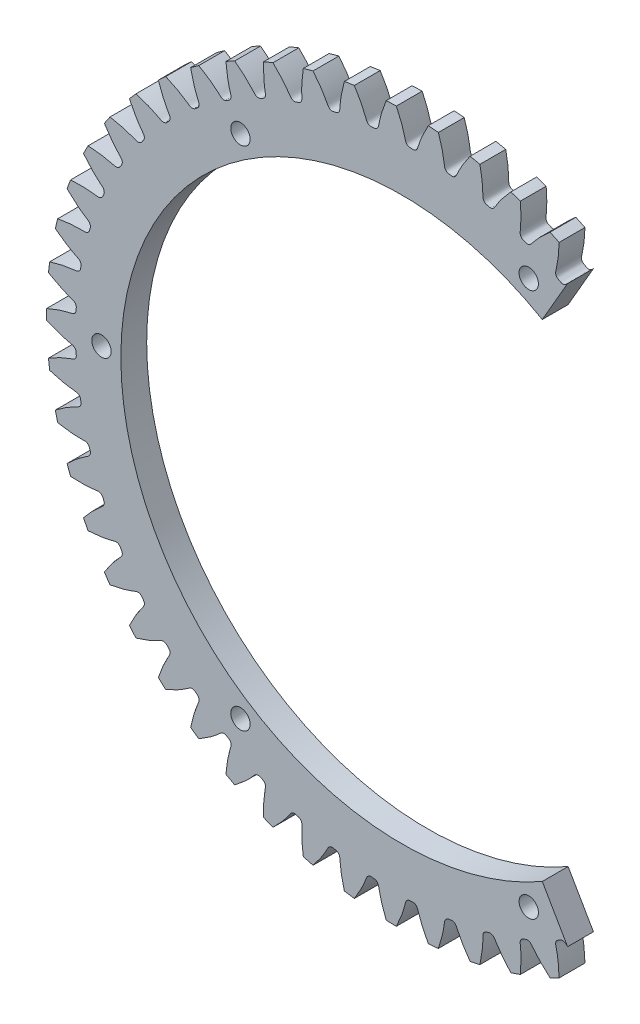
SolidWorks part; units mm, degrees
material "Thornel Mat VMA"
ref_plane "前视基准面" through (0, 0, 0) normal (0, 0, 1) x (1, 0, 0)
ref_plane "上视基准面" through (0, 0, 0) normal (0, 1, 0) x (1, 0, 0)
ref_plane "右视基准面" through (0, 0, 0) normal (1, 0, 0) x (0, 0, -1)
ref_axis "基准轴1" through (0, 0, 55) along (0, 0, -1)
sketch "旋转草图大直齿轮" plane through (0, 0, 0) normal (1, 0, 0) x (0, 0, -1)
  line L0 (0, 0) -> (1, 0) construction
  line L1 (-2, 0) -> (-2, 55)
  line L2 (-2, 55) -> (2, 55)
  line L3 (2, 55) -> (2, 0)
  line L4 (2, 0) -> (-2, 0)
revolve "大直齿轮" add sketch "旋转草图大直齿轮" angle 360 about L0
sketch "齿草图大直齿轮" plane through (0, 0, 0) normal (0, 0, 1) x (1, 0, 0)
  arc A0 (55.0418, 2.532) -> (55.0418, -2.532) centre (0, 0) cw
  spline S0 degree 3 poles (55.0418, -2.532) (54.9759, -2.4971) (54.8882, -2.451) (54.7785, -2.3944) (54.7135, -2.361) (54.6488, -2.3282) (54.5845, -2.2957) (54.5206, -2.2637) (54.457, -2.2321) (54.3937, -2.201) (54.3308, -2.1702) (54.2683, -2.1399) (54.2061, -2.1101) (54.1443, -2.0806) (54.0829, -2.0515) (54.0218, -2.0229) (53.9611, -1.9947) (53.9008, -1.9669) (53.8408, -1.9394) (53.7813, -1.9124) (53.7221, -1.8858) (53.6632, -1.8596) (53.6048, -1.8338) (53.5467, -1.8083) (53.4891, -1.7833) (53.4318, -1.7586) (53.3749, -1.7344) (53.3184, -1.7105) (53.2623, -1.6869) (53.2066, -1.6638) (53.1513, -1.641) (53.0964, -1.6186) (53.0418, -1.5966) (52.9877, -1.5749) (52.934, -1.5536) (52.8807, -1.5326) (52.8278, -1.512) (52.7753, -1.4918) (52.7232, -1.4719) (52.6716, -1.4523) (52.6203, -1.4331) (52.5695, -1.4143) (52.5191, -1.3957) (52.4691, -1.3776) (52.4195, -1.3597) (52.3703, -1.3422) (52.3216, -1.325) (52.2733, -1.3081) (52.2254, -1.2915) (52.178, -1.2753) (52.131, -1.2593) (52.0844, -1.2437) (52.0382, -1.2284) (51.9925, -1.2134) (51.9472, -1.1987) (51.9024, -1.1843) (51.858, -1.1702) (51.814, -1.1564) (51.7705, -1.1429) (51.7274, -1.1297) (51.6847, -1.1167) (51.6426, -1.1041) (51.6008, -1.0917) (51.5595, -1.0796) (51.5187, -1.0678) (51.4783, -1.0562) (51.4383, -1.0449) (51.3989, -1.0339) (51.3598, -1.0231) (51.3213, -1.0126) (51.2237, -0.9864) (51.1212, -0.9599) (51.0179, -0.9199) (50.9674, -0.898) (50.9165, -0.8729) (50.8647, -0.8436) (50.8114, -0.8087) (50.7562, -0.7664) (50.6993, -0.714) (50.6416, -0.6482) (50.5862, -0.5657) (50.5386, -0.4643) (50.5071, -0.3497) (50.495, -0.1924) (50.5033, 0) (50.495, 0.1924) (50.5071, 0.3497) (50.5386, 0.4643) (50.5862, 0.5657) (50.6416, 0.6482) (50.6993, 0.714) (50.7562, 0.7664) (50.8114, 0.8087) (50.8647, 0.8436) (50.9165, 0.8729) (50.9674, 0.898) (51.0179, 0.9199) (51.1212, 0.9599) (51.2237, 0.9864) (51.3213, 1.0126) (51.3598, 1.0231) (51.3989, 1.0339) (51.4383, 1.0449) (51.4783, 1.0562) (51.5187, 1.0678) (51.5595, 1.0796) (51.6008, 1.0917) (51.6426, 1.1041) (51.6847, 1.1167) (51.7274, 1.1297) (51.7705, 1.1429) (51.814, 1.1564) (51.858, 1.1702) (51.9024, 1.1843) (51.9472, 1.1987) (51.9925, 1.2134) (52.0382, 1.2284) (52.0844, 1.2437) (52.131, 1.2593) (52.178, 1.2753) (52.2254, 1.2915) (52.2733, 1.3081) (52.3216, 1.325) (52.3703, 1.3422) (52.4195, 1.3597) (52.4691, 1.3776) (52.5191, 1.3957) (52.5695, 1.4143) (52.6203, 1.4331) (52.6716, 1.4523) (52.7232, 1.4719) (52.7753, 1.4918) (52.8278, 1.512) (52.8807, 1.5326) (52.934, 1.5536) (52.9877, 1.5749) (53.0418, 1.5966) (53.0964, 1.6186) (53.1513, 1.641) (53.2066, 1.6638) (53.2623, 1.6869) (53.3184, 1.7105) (53.3749, 1.7344) (53.4318, 1.7586) (53.4891, 1.7833) (53.5467, 1.8083) (53.6048, 1.8338) (53.6632, 1.8596) (53.7221, 1.8858) (53.7813, 1.9124) (53.8408, 1.9394) (53.9008, 1.9669) (53.9611, 1.9947) (54.0218, 2.0229) (54.0829, 2.0515) (54.1443, 2.0806) (54.2061, 2.1101) (54.2683, 2.1399) (54.3308, 2.1702) (54.3937, 2.201) (54.457, 2.2321) (54.5206, 2.2637) (54.5845, 2.2957) (54.6488, 2.3282) (54.7135, 2.361) (54.7785, 2.3944) (54.8882, 2.451) (54.9759, 2.4971) (55.0418, 2.532) knots 0 0 0 0 0.02037 0.027067 0.033718 0.040323 0.046881 0.053393 0.059858 0.066278 0.072651 0.078977 0.085258 0.091492 0.09768 0.103821 0.109916 0.115965 0.121967 0.127923 0.133833 0.139697 0.145514 0.151284 0.157009 0.162687 0.168319 0.173904 0.179444 0.184937 0.190383 0.195783 0.201137 0.206445 0.211706 0.216921 0.22209 0.227212 0.232288 0.237318 0.242301 0.247238 0.252129 0.256973 0.261771 0.266523 0.271228 0.275887 0.2805 0.285066 0.289586 0.29406 0.298488 0.302869 0.307204 0.311492 0.315734 0.31993 0.32408 0.328183 0.33224 0.33625 0.340215 0.344132 0.348004 0.351829 0.355608 0.359341 0.363027 0.366667 0.370261 0.390614 0.395521 0.400505 0.405639 0.411019 0.416763 0.423025 0.429991 0.43787 0.446856 0.457049 0.468335 0.479114 0.5 0.520886 0.531665 0.542951 0.553144 0.56213 0.570009 0.576975 0.583237 0.588981 0.594361 0.599495 0.604479 0.609386 0.629739 0.633333 0.636973 0.640659 0.644392 0.648171 0.651996 0.655868 0.659785 0.66375 0.66776 0.671817 0.67592 0.68007 0.684266 0.688508 0.692796 0.697131 0.701512 0.70594 0.710414 0.714934 0.7195 0.724113 0.728772 0.733477 0.738229 0.743027 0.747871 0.752762 0.757699 0.762682 0.767712 0.772788 0.77791 0.783079 0.788294 0.793555 0.798863 0.804217 0.809617 0.815063 0.820556 0.826096 0.831681 0.837313 0.842991 0.848716 0.854486 0.860303 0.866167 0.872077 0.878033 0.884035 0.890084 0.896179 0.90232 0.908508 0.914742 0.921023 0.927349 0.933722 0.940142 0.946607 0.953119 0.959677 0.966282 0.972933 0.97963 1 1 1 1
extrude "齿拉伸切除大直齿轮" cut sketch "齿草图大直齿轮" against normal blind 2 and the other way blind 2
pattern_circular "齿形大直齿轮" count 53 every 6.792 about axis through (0, 0, 55) along (0, 0, -1) of "齿拉伸切除大直齿轮"
sketch "辅助草图大直齿轮" plane through (0, 0, 0) normal (0, 0, 1) x (1, 0, 0)
  circle A0 centre (0, 0) radius 53 construction
  circle A1 centre (0, 0) radius 49.8037 construction
  circle A2 centre (0, 0) radius 51.2224 construction
  circle A3 centre (0, 0) radius 55 construction
  circle A4 centre (0, 0) radius 50.5 construction
  dimension "PitchDiameter" = 106
  dimension "BaseDiameter" = 99.6074
  dimension "FormDiameter" = 102.4448
  dimension "MajorDiameter" = 110
  dimension "MinorDiameter" = 101
sketch "草图1" plane through (0, 0, 2) normal (0, 0, 1) x (1, 0, 0)
  line L0 (21.75, 37.6721) -> (27.5, 47.6314)
  line L1 (0, 0) -> (19.9812, 0) construction
  line L2 (21.75, -37.6721) -> (27.5, -47.6314)
  line L3 (-46.5, 0) -> (0, 0) construction
  line L4 (-24.9844, 39.2177) -> (0, 0) construction
  line L5 (19.6517, 42.1433) -> (0, 0) construction
  arc A1 (21.75, 37.6721) -> (21.75, -37.6721) centre (0, 0) ccw
  circle A2 centre (0, 0) radius 55 construction
  arc A3 (27.5, 47.6314) -> (27.5, -47.6314) centre (0, 0) cw
  circle A4 centre (0, 0) radius 46.5 construction
  circle A5 centre (-46.5, 0) radius 1.5
  circle A6 centre (19.6517, 42.1433) radius 1.5
  circle A7 centre (-24.9844, 39.2177) radius 1.5
  circle A8 centre (19.6517, -42.1433) radius 1.5
  circle A9 centre (-24.9844, -39.2177) radius 1.5
  dimension "D1" = 87
  dimension "D4" = 3
  dimension "D5" = 3
  dimension "D2" = 60
  dimension "D3" = 115
extrude "切除-拉伸1" cut sketch "草图1" against normal blind 10
